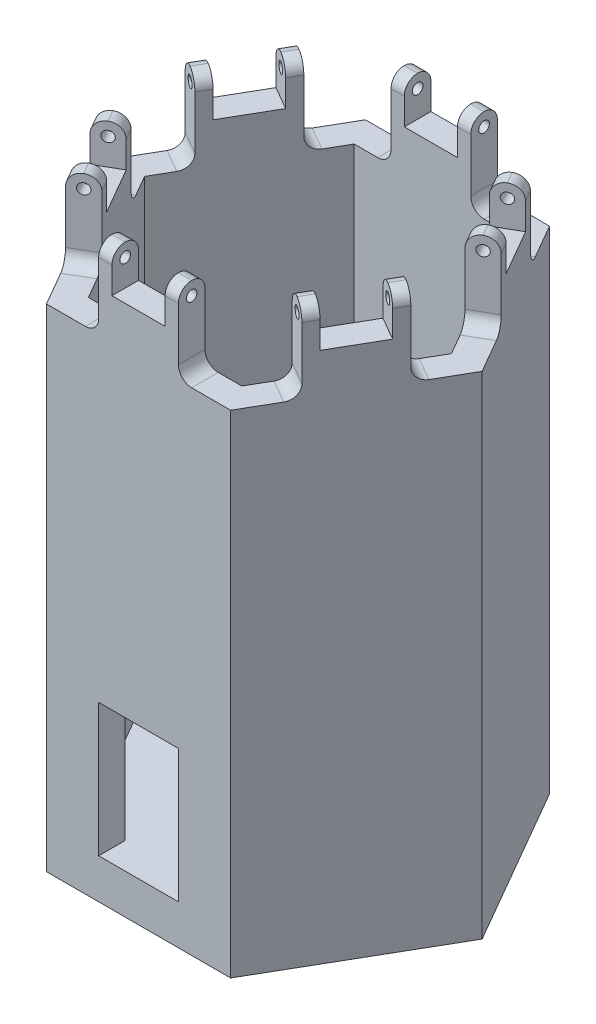
SolidWorks part; units mm, degrees
ref_plane "Front Plane" through (0, 0, 0) normal (0, 0, 1) x (1, 0, 0)
ref_plane "Top Plane" through (0, 0, 0) normal (0, 1, 0) x (1, 0, 0)
ref_plane "Right Plane" through (0, 0, 0) normal (1, 0, 0) x (0, 0, -1)
sketch "Sketch1" plane through (0, 0, 0) normal (0, 1, 0) x (1, 0, 0)
  line L0 (-69.282, 0) -> (-34.641, 60)
  line L1 (-34.641, 60) -> (34.641, 60)
  line L2 (34.641, 60) -> (69.282, 0)
  line L3 (69.282, 0) -> (34.641, -60)
  line L4 (34.641, -60) -> (-34.641, -60)
  line L5 (-34.641, -60) -> (-69.282, 0)
  line L6 (34.641, 60) -> (-34.641, -60) construction
  line L7 (-34.641, 60) -> (34.641, -60) construction
  line L8 (-69.282, 0) -> (69.282, 0) construction
  point P2 (0, 0)
  dimension "D1" = 120
  dimension "D2" = 120
  dimension "D3" = 120
extrude "Boss-Extrude1" add sketch "Sketch1" along normal blind 15 contours L1 L2 L3 L4 L5 L0
sketch "Sketch4" plane through (0, 15, 0) normal (0, 1, 0) x (1, 0, 0)
  line L1 (-34.641, -60) -> (34.641, -60)
  line L3 (-28.8675, -50) -> (28.8675, -50)
  line L4 (-69.282, 0) -> (-57.735, 0)
  line L5 (-57.735, 0) -> (-28.8675, -50)
  line L6 (-69.282, 0) -> (-34.641, -60)
  line L7 (28.8675, -50) -> (57.735, 0)
  line L8 (57.735, 0) -> (69.282, 0)
  line L9 (69.282, 0) -> (34.641, -60)
  line L10 (0, 0) -> (-34.641, -60) construction
  line L11 (0, 0) -> (34.641, -60) construction
  dimension "D1" = 10
extrude "Boss-Extrude3" add sketch "Sketch4" along normal blind 170
mirror "Mirror1" about plane through (57.735, 185, 0) normal (0, 0, 1) of "Boss-Extrude3"
sketch "Sketch5" plane through (0, 185, 0) normal (0, 1, 0) x (1, 0, 0)
  line L0 (28.8675, -50) -> (-28.8675, -50) construction
  line L1 (-15, -50) -> (15, -50)
  line L2 (-15, -50) -> (-15, -60)
  line L3 (-15, -60) -> (15, -60)
  line L4 (15, -50) -> (15, -60)
  line L5 (-34.641, -60) -> (34.641, -60) construction
  point P8 (0, -50)
  dimension "D1" = 30
extrude "Boss-Extrude4" add sketch "Sketch5" along normal blind 30 contours L2 L3 L4 L1
pattern_circular "CirPattern2" count 6 over 360 about axis through (0, 0, 0) along (0, 1, 0) of "Boss-Extrude4"
sketch "Sketch7" plane through (-51.9615, 0, 30) normal (-0.866, 0, 0.5) x (0.5, 0, 0.866)
  line L0 (-15, 215) -> (15, 215) construction
  line L1 (-10, 215) -> (10, 215)
  line L2 (-10, 215) -> (-10, 200)
  line L3 (-10, 200) -> (10, 200)
  line L4 (10, 215) -> (10, 200)
  point P6 (0, 200)
  dimension "D1" = 20
  dimension "D2" = 15
extrude "Cut-Extrude1" cut sketch "Sketch7" against normal up to next contours L4 L3 L2 L1
pattern_circular "CirPattern4" count 6 over 360 about axis through (0, 0, 0) along (0, 1, 0) of "Cut-Extrude1"
fillet "Fillet1" radius 5 60 edges at (-49.5513, 215, 14.1747) (-55.1314, 185, 14.5096) (-40.1314, 215, 40.4904) (-55.1314, 215, 14.5096) (-58.2115, 215, 19.1747) (-40.1314, 185, 40.4904) (-37.0513, 215, -35.8253) (-40.1314, 185, -40.4904) (-55.1314, 215, -14.5096) (-40.1314, 215, -40.4904) (-45.7115, 215, -40.8253) (-55.1314, 185, -14.5096) (12.5, 215, -50) (15, 185, -55) (-15, 215, -55) (15, 215, -55) (12.5, 215, -60) (-15, 185, -55) (49.5513, 215, -14.1747) (55.1314, 185, -14.5096) (40.1314, 215, -40.4904) (55.1314, 215, -14.5096) (58.2115, 215, -19.1747) (40.1314, 185, -40.4904) (37.0513, 215, 35.8253) (40.1314, 185, 40.4904) (55.1314, 215, 14.5096) (40.1314, 215, 40.4904) (45.7115, 215, 40.8253) (55.1314, 185, 14.5096) (-37.0513, 215, 35.8253) (-45.7115, 215, 40.8253) (-52.6314, 215, 18.8397) (-42.6314, 215, 36.1603) (49.5513, 215, 14.1747) (58.2115, 215, 19.1747) (-49.5513, 215, -14.1747) (-58.2115, 215, -19.1747) (-12.5, 215, -50) (-12.5, 215, -60) (37.0513, 215, -35.8253) (45.7115, 215, -40.8253) (12.5, 215, 50) (12.5, 215, 60) (-10, 215, 55) (10, 215, 55) (42.6314, 215, 36.1603) (52.6314, 215, 18.8397) (52.6314, 215, -18.8397) (42.6314, 215, -36.1603) (-10, 215, -55) (10, 215, -55) (-52.6314, 215, -18.8397) (-42.6314, 215, -36.1603) (-12.5, 215, 50) (-15, 185, 55) (15, 215, 55) (-15, 215, 55) (-12.5, 215, 60) (15, 185, 55)
hole_wizard "Ø4.0 mm Dowel Holes1" positions "Sketch8" profile "Sketch10" hole size "Ø4.0" standard "ISO" end condition through all
sketch "Sketch8" plane through (15, 0, 0) normal (1, 0, 0) x (0, 0, -1)
  point P0 (-55, 210)
sketch "Sketch10" plane through (15, 210, 55) normal (0, 1, 0) x (0, 0, -1)
  line L0 (0, 0) -> (0, 84.282)
  line L1 (0, 84.282) -> (2, 84.282)
  line L2 (2, 84.282) -> (2, 0)
  line L5 (2, 0) -> (0, 0)
  line L11 (0, -6.35) -> (0, 107.95) construction
  dimension "Thru Hole Dia." = 4
  dimension "Thru Hole Depth" = 84.282
pattern_circular "CirPattern8" count 6 over 360 about axis through (0, 15, 0) along (0, -1, 0) of "Ø4.0 mm Dowel Holes1"
sketch "Sketch11" plane through (0, 0, 60) normal (0, 0, 1) x (1, 0, 0)
  line L1 (-15, 15) -> (15, 15)
  line L2 (-15, 15) -> (-15, 65)
  line L3 (-15, 65) -> (15, 65)
  line L4 (15, 15) -> (15, 65)
  line L5 (28.8675, 15) -> (-28.8675, 15) construction
  point P6 (0, 15)
  dimension "D1" = 30
  dimension "D2" = 50
extrude "Cut-Extrude2" cut sketch "Sketch11" against normal up to next contours L3 L4 L1 L2
sketch "Sketch12" plane through (0, 0, 0) normal (0, -1, 0) x (1, 0, 0)
  line L1 (-15.52, 15.52) -> (15.52, 15.52) construction
  line L2 (-15.52, 15.52) -> (-15.52, -15.52) construction
  line L3 (-15.52, -15.52) -> (15.52, -15.52) construction
  line L4 (15.52, 15.52) -> (15.52, -15.52) construction
  point P4 (0, 15.52)
  point P6 (15.52, 0)
  dimension "D1" = 31.04
hole_wizard "M3 Clearance Hole1" positions "Sketch13" profile "Sketch14" hole size "M3" standard "ISO" end condition up to next
sketch "Sketch13" plane through (0, 0, 0) normal (0, -1, 0) x (-1, 0, 0)
  point P0 (-15.52, 15.52)
sketch "Sketch14" plane through (15.52, 0, -15.52) normal (1, 0, 0) x (0, 0, -1)
  line L0 (0, 0) -> (0, 15)
  line L1 (0, 15) -> (1.8, 15)
  line L2 (1.8, 15) -> (1.8, 0)
  line L5 (1.8, 0) -> (0, 0)
  line L11 (0, -6.35) -> (0, 107.95) construction
  dimension "Thru Hole Dia." = 3.6
  dimension "Thru Hole Depth" = 15
pattern_linear "LPattern1" count 2 spacing 31.04 along (-1, 0, 0) count 2 spacing 31.04 along (0, 0, 1) of "M3 Clearance Hole1"
